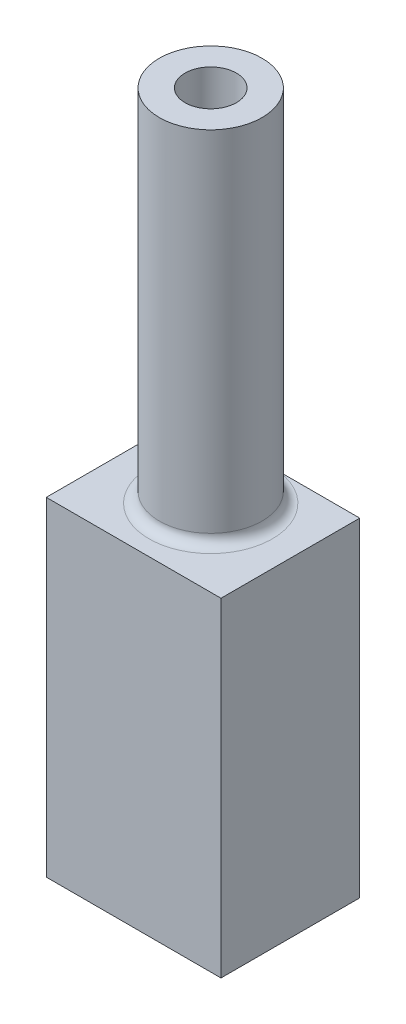
SolidWorks part; units mm, degrees
ref_plane "Front Plane" through (0, 0, 0) normal (0, 0, 1) x (1, 0, 0)
ref_plane "Top Plane" through (0, 0, 0) normal (0, 1, 0) x (1, 0, 0)
ref_plane "Right Plane" through (0, 0, 0) normal (1, 0, 0) x (0, 0, -1)
sketch "Sketch1" plane through (0, 0, 0) normal (0, 0, 1) x (1, 0, 0)
  line L0 (-6.5, -14) -> (-6.5, 14)
  line L1 (-8.5, -16) -> (-4.5, -16)
  line L2 (-8.5, -16) -> (-8.5, 16)
  line L3 (-8.5, 16) -> (8.5, 16)
  line L4 (8.5, -16) -> (8.5, 16)
  line L5 (-8.5, -16) -> (8.5, 16) construction
  line L6 (-8.5, 16) -> (8.5, -16) construction
  line L7 (-6.5, 14) -> (6.5, 14)
  line L8 (6.5, -14) -> (6.5, 14)
  line L9 (-6.5, -14) -> (-4.5, -14)
  line L10 (-4.5, -14) -> (-4.5, -16)
  line L11 (4.5, -14) -> (4.5, -16)
  line L12 (4.5, -14) -> (6.5, -14)
  line L13 (-6.5, -14) -> (6.5, -14) construction
  line L14 (4.5, -16) -> (8.5, -16)
  line L15 (-8.5, -16) -> (8.5, -16) construction
  point P0 (0, 0)
  dimension "D1" = 17
  dimension "D2" = 32
  dimension "D4" = 4
  dimension "D5" = 4
  dimension "D3" = 2
extrude "Boss-Extrude1" add sketch "Sketch1" along normal mid plane 12
sketch "Sketch2" plane through (0, 16, 0) normal (0, 1, 0) x (1, 0, 0)
  circle A0 centre (0, 0) radius 5
  dimension "D1" = 10
extrude "Boss-Extrude2" add sketch "Sketch2" along normal blind 35
fillet "Fillet1" radius 1 1 edges at (0, 16, 5)
sketch "Sketch3" plane through (0, 0, 6) normal (0, 0, 1) x (1, 0, 0)
  line L1 (-8.5, 16) -> (8.5, 16)
  line L2 (-8.5, 16) -> (-8.5, -16)
  line L3 (-8.5, -16) -> (8.5, -16)
  line L4 (8.5, 16) -> (8.5, -16)
extrude "Boss-Extrude3" add sketch "Sketch3" along normal blind 1.5
sketch "Sketch4" plane through (0, 51, 0) normal (0, 1, 0) x (1, 0, 0)
  circle A0 centre (0, 0) radius 2.5
  dimension "D1" = 5
extrude "Cut-Extrude1" cut sketch "Sketch4" against normal up to next
